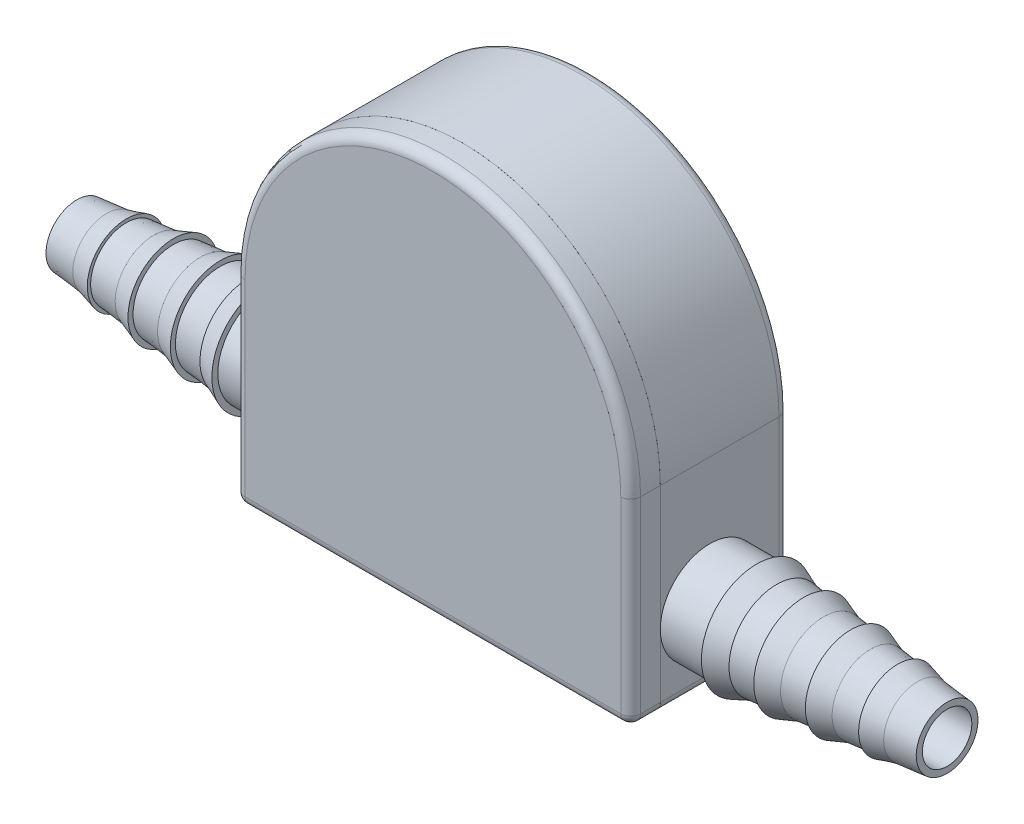
SolidWorks part; units mm, degrees
ref_plane "Front Plane" through (0, 0, 0) normal (0, 0, 1) x (1, 0, 0)
ref_plane "Top Plane" through (0, 0, 0) normal (0, 1, 0) x (1, 0, 0)
ref_plane "Right Plane" through (0, 0, 0) normal (1, 0, 0) x (0, 0, -1)
sketch "Sketch1" plane through (0, 0, 0) normal (0, 0, 1) x (1, 0, 0)
  line L0 (-44, -12.6) -> (44, -12.6) construction
  line L1 (0, -7.6) -> (0, -17.6) construction
  line L2 (-9.6417, 15.1999) -> (-2.1997, 2.31) construction
  line L3 (39, -8.65) -> (39, -16.55) construction
  line L4 (-9, 15.5885) -> (0, 0) construction
  line L5 (-17.9844, 0.75) -> (-3.1004, 0.75) construction
  line L6 (-0.9007, 3.06) -> (-8.3427, 15.9499) construction
  line L7 (0.9007, 3.06) -> (8.3427, 15.9499) construction
  line L8 (34.25, -8.0119) -> (34.25, -17.1881) construction
  line L9 (29.5, -7.5492) -> (29.5, -17.6508) construction
  line L10 (24.75, -7) -> (24.75, -18.2) construction
  line L11 (39, -8.65) -> (34.25, -8.65) construction
  line L12 (34.25, -8.65) -> (29.5, -8.65) construction
  line L13 (29.5, -8.65) -> (24.75, -8.65) construction
  line L14 (44, -9.475) -> (44, -15.725) construction
  line L15 (0, -7.6) -> (24.75, -7.6) construction
  line L16 (24.75, -7.6) -> (44, -9.475) construction
  line L17 (39, -8.65) -> (41, -9.1828) construction
  line L18 (34.25, -8.0119) -> (36.25, -8.7201) construction
  line L19 (29.5, -7.5492) -> (31.5, -8.2575) construction
  line L20 (24.75, -7) -> (26.75, -7.7948) construction
  line L21 (12, -16.2) -> (17, -16.2)
  line L22 (12, -16.2) -> (12, -18.6)
  line L23 (17, -16.2) -> (17, -18.6)
  line L24 (12, -18.6) -> (17, -18.6)
  line L25 (20, 0) -> (20, -20) construction
  line L26 (20, -20) -> (0, -20) construction
  line L27 (26.75, -7.7948) -> (24.75, -7.7948) construction
  line L28 (31.5, -8.2575) -> (29.5, -8.2575) construction
  line L29 (36.25, -8.7201) -> (34.25, -8.7201) construction
  line L30 (41, -9.1828) -> (39, -9.1828) construction
  circle A0 centre (0, 0) radius 20
  circle A1 centre (0, 0) radius 18 construction
  circle A3 centre (0, 0) radius 1.25
  arc A4 (-0.9007, 3.06) -> (0.9007, 3.06) centre (0, 3.58) ccw construction
  circle A5 centre (0, 0) radius 2.54 construction
  arc A6 (-2.1997, 2.31) -> (-3.1004, 0.75) centre (-3.1004, 1.79) cw construction
  point P5 (0, -12.6)
  point P36 (44, -10.1)
  dimension "Height" = 40
  dimension "D5" = 2.5
  dimension "D8" = 5.08
  dimension "End to End Length" = 88
  dimension "D2" = 10
  dimension "D3" = 2.4
  dimension "Approx Wall Thickness" = 2
  dimension "D6" = 0.75
  dimension "D7" = 60
  dimension "D9" = 60
  dimension "D10" = 5
  dimension "D11" = 4.75
  dimension "D12" = 7.9
  dimension "For Tube ID Min" = 6.25
  dimension "Thru Hole Dia" = 5
  dimension "D14" = 2
  dimension "D15" = 3
  dimension "D16" = 5
  dimension "D17" = 2.4
  dimension "D18" = 1.4
  dimension "For Tube ID Max" = 11.2
  dimension "D13" = 19.5
sketch "Sketch2" plane through (0, 0, 0) normal (1, 0, 0) x (0, 0, -1)
  line L0 (-8, 0) -> (8, 0) construction
  point P3 (-6, 0)
  dimension "Width" = 16
  dimension "D2" = 2
sketch "Sketch3" plane through (0, 0, 0) normal (0, 0, 1) x (1, 0, 0)
  line L0 (20, -20) -> (0, -20) construction
  line L1 (20, 0) -> (20, -20) construction
  line L2 (20, -20) -> (-20, -20)
  line L3 (20, 0) -> (20, -20)
  line L4 (-20, 0) -> (-20, -20)
  circle A0 centre (0, 0) radius 20 construction
  arc A1 (20, 0) -> (-20, 0) centre (0, 0) ccw
extrude "Boss-Extrude1" add sketch "Sketch3" against normal up to vertex (8 mm away) from vertex up to point (0, 0, -8) starting at point (0, 0, 8)
sketch "Sketch4" plane through (0, 0, 0) normal (0, 0, 1) x (1, 0, 0)
  line L0 (44, -9.475) -> (44, -15.725) construction
  line L1 (39, -8.65) -> (41, -9.1828) construction
  line L2 (39, -8.65) -> (39, -16.55) construction
  line L3 (34.25, -8.0119) -> (36.25, -8.7201) construction
  line L4 (34.25, -8.0119) -> (34.25, -17.1881) construction
  line L5 (29.5, -7.5492) -> (31.5, -8.2575) construction
  line L6 (29.5, -7.5492) -> (29.5, -17.6508) construction
  line L7 (24.75, -7.6) -> (44, -9.475) construction
  line L8 (24.75, -7) -> (26.75, -7.7948) construction
  line L9 (24.75, -7) -> (24.75, -18.2) construction
  line L10 (0, -7.6) -> (24.75, -7.6) construction
  line L11 (44, -9.475) -> (44, -10.1)
  line L12 (39, -8.65) -> (41, -9.1828)
  line L13 (39, -8.65) -> (39, -8.988)
  line L14 (34.25, -8.0119) -> (36.25, -8.7201)
  line L15 (34.25, -8.0119) -> (34.25, -8.5253)
  line L16 (29.5, -7.5492) -> (31.5, -8.2575)
  line L17 (29.5, -7.5492) -> (29.5, -8.0627)
  line L18 (26.75, -7.7948) -> (29.5, -8.0627)
  line L19 (24.75, -7) -> (26.75, -7.7948)
  line L20 (24.75, -7) -> (24.75, -7.6)
  line L21 (-24.75, -7.6) -> (24.75, -7.6)
  line L22 (44, -10.1) -> (-44, -10.1)
  line L23 (0, -7.6) -> (0, -17.6) construction
  line L24 (0, -10.1) -> (0, -7.6) construction
  line L25 (31.5, -8.2575) -> (34.25, -8.5253)
  line L26 (36.25, -8.7201) -> (39, -8.988)
  line L27 (41, -9.1828) -> (44, -9.475)
  line L28 (-41, -9.1828) -> (-44, -9.475)
  line L29 (-36.25, -8.7201) -> (-39, -8.988)
  line L30 (-31.5, -8.2575) -> (-34.25, -8.5253)
  line L31 (-24.75, -7) -> (-24.75, -7.6)
  line L32 (-24.75, -7) -> (-26.75, -7.7948)
  line L33 (-26.75, -7.7948) -> (-29.5, -8.0627)
  line L34 (-29.5, -7.5492) -> (-29.5, -8.0627)
  line L35 (-29.5, -7.5492) -> (-31.5, -8.2575)
  line L36 (-34.25, -8.0119) -> (-34.25, -8.5253)
  line L37 (-34.25, -8.0119) -> (-36.25, -8.7201)
  line L38 (-39, -8.65) -> (-39, -8.988)
  line L39 (-39, -8.65) -> (-41, -9.1828)
  line L40 (-44, -9.475) -> (-44, -10.1)
revolve "Revolve1" add sketch "Sketch4" angle 360 about L0
fillet "Fillet1" radius 1 10 edges at (20, -10, -8) (-20, -10, -8) (20, -10, 8) (-20, -10, 8) (20, -20, 0) (0, -20, -8) (-20, -20, 0) (0, -20, 8) (0, 20, -8) (0, 20, 8)
sketch "Sketch5" plane through (20, 0, 0) normal (1, 0, 0) x (0, 0, -1)
  line L0 (-5, -25.4) -> (-5, 25.4)
  line L1 (-8, 0) -> (8, 0) construction
  line L2 (-8, 0) -> (8, 0) construction
  circle A0 centre (0, -12.6) radius 5 construction
  dimension "D1" = 50.8
extrude "Cut-Extrude-Thin1" cut sketch "Sketch5" against normal up to surface (40 mm away) thin up to face at (-20, -9.5, 0) thin type one direction reverse wall 0.0025
shell "Shell1" thickness 2 removed face at (0, -9.7357, 5.0025)
other "DeleteFace1" face at (-18, -9, 5.5013) face at (0, -18, 5.5013) face at (18, -9, 5.5013) and patch yes
sketch "Sketch6" plane through (0, 0, 5) normal (0, 0, 1) x (1, 0, 0)
  line L0 (-18, -10.1) -> (18, -10.1)
  line L1 (-18, -10.1) -> (-18, -15.1)
  line L2 (18, -10.1) -> (18, -15.1)
  line L3 (-18, -15.1) -> (18, -15.1)
  line L4 (-44, -12.6) -> (44, -12.6) construction
  circle A0 centre (0, 0) radius 18
  circle A1 centre (0, 0) radius 18 construction
  point P8 (18, -12.6)
extrude "Cut-Extrude2" cut sketch "Sketch6" against normal offset from surface (11 mm away) 2 contours L0 A0 | A0 L0 L1 L3 | L3 A0 | A0 L3 L2 L0 | L0 L1 L3 L2 region at (-15.1453, -12.9938, 5) region at (0, 2.5867, 5) region at (15.1453, -12.9938, 5) region at (0, -16.2684, 5) up to face at (0, -4.75, -8)
sketch "Sketch7" plane through (0, 0, -8) normal (0, 0, -1) x (-1, 0, 0)
  line L0 (-12, -16.2) -> (-12, -18.6) construction
  line L1 (-12, -18.6) -> (-17, -18.6) construction
  line L2 (-17, -16.2) -> (-17, -18.6) construction
  line L3 (-12, -16.2) -> (-17, -16.2) construction
  line L4 (-12, -16.2) -> (-12, -18.6)
  line L5 (-12, -18.6) -> (-17, -18.6)
  line L6 (-17, -16.2) -> (-17, -18.6)
  line L7 (-12, -16.2) -> (-17, -16.2)
  line L8 (0, -7.6) -> (0, -17.6) construction
  line L9 (0, -7.6) -> (0, -17.6) construction
  line L10 (12, -16.2) -> (17, -16.2)
  line L11 (17, -16.2) -> (17, -18.6)
  line L12 (12, -18.6) -> (17, -18.6)
  line L13 (12, -16.2) -> (12, -18.6)
extrude "Cut-Extrude3" cut sketch "Sketch7" against normal blind 6.6 draft 1
sketch "Sketch8" plane through (44, 0, 0) normal (1, 0, 0) x (0, 0, -1)
  circle A0 centre (0, -12.6) radius 2.5 construction
  circle A1 centre (0, -12.6) radius 2.5
extrude "Cut-Extrude4" cut sketch "Sketch8" against normal through all
sketch "Sketch9" plane through (0, 0, -6) normal (0, 0, 1) x (1, 0, 0)
  circle A0 centre (0, 0) radius 1.25 construction
  circle A1 centre (0, 0) radius 1.25
extrude "Boss-Extrude2" add sketch "Sketch9" along normal blind 3 draft 1
fillet "Fillet2" radius 1 1 edges at (1.25, 0, -6)
sketch "Sketch10" plane through (0, 0, 6) normal (0, 0, -1) x (-1, 0, 0)
  circle A0 centre (0, 0) radius 1.25 construction
  circle A1 centre (0, 0) radius 1.25
extrude "Boss-Extrude3" add sketch "Sketch10" along normal blind 3 draft 1
fillet "Fillet3" radius 1 1 edges at (1.25, 0, 6)
sketch "Sketch11" plane through (0, 0, 0) normal (0, 0, 1) x (1, 0, 0)
  line L0 (-17.9844, 0.75) -> (-3.1004, 0.75) construction
  line L1 (-9.6417, 15.1999) -> (-2.1997, 2.31) construction
  line L2 (-17.4839, 0.75) -> (-3.1004, 0.75)
  line L3 (-9.3915, 14.7665) -> (-2.1997, 2.31)
  line L4 (9.3915, 14.7665) -> (2.1997, 2.31)
  line L5 (17.4839, 0.75) -> (3.1004, 0.75)
  line L6 (8.0924, -15.5165) -> (0.9007, -3.06)
  line L7 (-8.0924, -15.5165) -> (-0.9007, -3.06)
  arc A0 (-3.1004, 0.75) -> (-2.1997, 2.31) centre (-3.1004, 1.79) ccw construction
  arc A1 (-3.1004, 0.75) -> (-2.1997, 2.31) centre (-3.1004, 1.79) ccw
  arc A2 (9.3915, 14.7665) -> (-9.3915, 14.7665) centre (0, 0) ccw
  circle A3 centre (0, 0) radius 18 construction
  arc A4 (2.1997, 2.31) -> (3.1004, 0.75) centre (3.1004, 1.79) ccw
  arc A5 (0.9007, -3.06) -> (-0.9007, -3.06) centre (0, -3.58) ccw
  arc A6 (8.0924, -15.5165) -> (17.4839, 0.75) centre (0, 0) ccw
  arc A7 (-17.4839, 0.75) -> (-8.0924, -15.5165) centre (0, 0) ccw
  circle A8 centre (0, 0) radius 1.25 construction
  circle A9 centre (0, 0) radius 1.25
  point P24 (0, 0)
  dimension "D1" = 0.5
  dimension "D3" = 60
  dimension "D2" = 3
extrude "Boss-Extrude4" add sketch "Sketch11" along normal offset from surface (4 mm away) 1 from offset 1 separate body up to face at (2.2327, 0, 6)
chamfer "Chamfer1" distance 2.5 angle 45 3 edges at (0, 17.5, 5) (-15.1554, -8.75, 5) (15.1554, -8.75, 5)
sketch "Sketch12" plane through (0, 0, 5) normal (0, 0, 1) x (1, 0, 0)
  line L0 (0.9007, 3.06) -> (8.3427, 15.9499) construction
  line L1 (-0.9007, 3.06) -> (-8.3427, 15.9499) construction
  line L2 (0.9007, 3.06) -> (8.3427, 15.9499)
  line L3 (-0.9007, 3.06) -> (-8.3427, 15.9499)
  line L4 (3.1004, -0.75) -> (17.9844, -0.75)
  line L5 (2.1997, -2.31) -> (9.6417, -15.1999)
  line L6 (-2.1997, -2.31) -> (-9.6417, -15.1999)
  line L7 (-3.1004, -0.75) -> (-17.9844, -0.75)
  arc A0 (-0.9007, 3.06) -> (0.9007, 3.06) centre (0, 3.58) ccw construction
  arc A1 (-0.9007, 3.06) -> (0.9007, 3.06) centre (0, 3.58) ccw
  arc A2 (14.8993, -10.1) -> (-14.8993, -10.1) centre (0, 0) ccw construction
  arc A3 (8.3427, 15.9499) -> (-8.3427, 15.9499) centre (0, 0) ccw
  arc A4 (3.1004, -0.75) -> (2.1997, -2.31) centre (3.1004, -1.79) ccw
  arc A5 (9.6417, -15.1999) -> (17.9844, -0.75) centre (0, 0) ccw
  arc A6 (-2.1997, -2.31) -> (-3.1004, -0.75) centre (-3.1004, -1.79) ccw
  arc A7 (-17.9844, -0.75) -> (-9.6417, -15.1999) centre (0, 0) ccw
  point P20 (0, 0)
  dimension "D1" = 3
extrude "Cut-Extrude5" cut sketch "Sketch12" against normal offset from surface (3.75 mm away) 0.25 up to face at (0, 0, 1)
fillet "Fillet4" radius 0.25 22 edges at (-5.7956, -8.5383, 1.25) (-2.1997, -1.27, 1.25) (5.7956, -8.5383, 1.25) (2.1997, -1.27, 1.25) (-4.4966, 9.2883, 1.25) (0, 2.54, 1.25) (1.25, 0, 5) (-8.75, -15.1554, 2.5) (-7.5, -12.9904, 5) (-17.5, 0, 2.5) (-15, 0, 5) (-10.2921, -0.75, 1.25) (10.2921, -0.75, 1.25) (8.75, -15.1554, 2.5) (7.5, -12.9904, 5) (17.5, 0, 2.5) (15, 0, 5) (8.75, 15.1554, 2.5) (7.5, 12.9904, 5) (-7.5, 12.9904, 5) (4.4966, 9.2883, 1.25) (-8.75, 15.1554, 2.5)
fillet "Fillet5" radius 0.1 75 edges at (-9.3915, 14.7665, 1.6982) (-9.3791, 14.7451, 2.5048) (-8.1298, 12.5812, 4.9859) (-5.144, 7.4097, 5) (-2.1997, 1.27, 5) (-17.4839, 0.75, 1.6982) (-17.4698, 0.75, 2.4791) (-14.9859, 0.75, 4.9754) (-2.1997, -1.27, 5) (-5.144, -7.4097, 5) (-8.1425, -12.6032, 4.9754) (-9.3844, -14.7543, 2.4791) (-9.3915, -14.7665, 1.9482) (-9.4376, -14.7371, 1.3439) (-15.1554, -8.75, 1.25) (-17.4797, -0.8437, 1.3049) (-17.4839, -0.75, 1.9482) (-17.4592, -0.75, 2.5048) (-14.9605, -0.75, 4.9859) (0, 2.54, 5) (-3.845, 8.1597, 5) (-6.8434, 13.3532, 4.9754) (-8.0854, 15.5043, 2.4791) (-8.0924, 15.5165, 1.9482) (-8.0439, 15.5418, 1.3439) (0, 17.5, 1.25) (8.0092, 15.5597, 1.3049) (8.0924, 15.5165, 1.9482) (8.0801, 15.4951, 2.5048) (6.8307, 13.3312, 4.9859) (17.4839, 0.75, 1.6982) (17.4592, 0.75, 2.5048) (14.9605, 0.75, 4.9859) (8.989, 0.75, 5) (2.1997, 1.27, 5) (9.3915, 14.7665, 1.6982) (9.3844, 14.7543, 2.4791) (8.1425, 12.6032, 4.9754) (14.9859, -0.75, 4.9754) (17.4698, -0.75, 2.4791) (17.4839, -0.75, 1.9482) (17.4815, -0.8047, 1.3439) (15.1554, -8.75, 1.25) (9.4705, -14.716, 1.3049) (9.3915, -14.7665, 1.9482) (9.3791, -14.7451, 2.5048) (8.1298, -12.5812, 4.9859) (5.144, -7.4097, 5) (2.1997, -1.27, 5) (-8.0924, -15.5165, 1.6982) (-8.0801, -15.4951, 2.5048) (-6.8307, -13.3312, 4.9859) (-3.845, -8.1597, 5) (0, -2.54, 5) (8.0924, -15.5165, 1.6982) (8.0854, -15.5043, 2.4791) (6.8434, -13.3532, 4.9754) (-8.989, 0.75, 5) (-8.989, -0.75, 5) (3.845, 8.1597, 5) (5.144, 7.4097, 5) (8.989, -0.75, 5) (3.845, -8.1597, 5)
mirror "Mirror1" about plane through (-3.1004, 1.79, 1) normal (0, 0, 1) of bodies 117
equation "\"D2@Sketch2\" = \"Approx Wall Thickness@Sketch1\""
